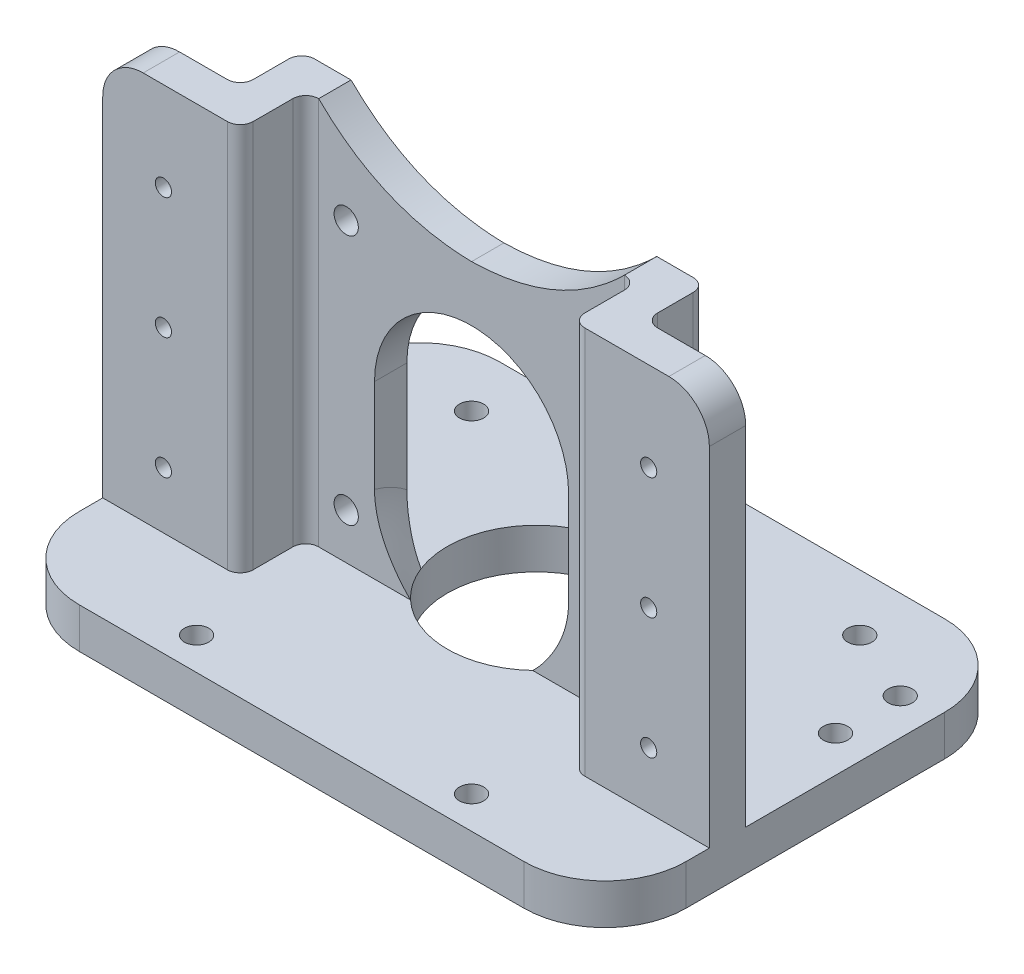
SolidWorks part; units mm, degrees
material "聚脂树脂"
ref_plane "前视基准面" through (0, 0, 0) normal (0, 0, 1) x (1, 0, 0)
ref_plane "上视基准面" through (0, 0, 0) normal (0, 1, 0) x (1, 0, 0)
ref_plane "右视基准面" through (0, 0, 0) normal (1, 0, 0) x (0, 0, -1)
other "Configuration Table"
sketch "草图1" plane through (0, 0, 0) normal (0, 1, 0) x (1, 0, 0)
  line L0 (0, 0) -> (58.6016, 0) construction
  line L1 (-37.5, -29) -> (37.5, -29)
  line L2 (-37.5, -29) -> (-37.5, 29)
  line L3 (-37.5, 29) -> (37.5, 29)
  line L4 (37.5, -29) -> (37.5, 29)
  line L5 (-37.5, -29) -> (37.5, 29) construction
  line L6 (-37.5, 29) -> (37.5, -29) construction
  line L7 (0, 0) -> (0, 47.0411) construction
  line L8 (0, 5) -> (44.8156, 5) construction
  circle A0 centre (0, 0) radius 11
  circle A1 centre (24, 16) radius 1.5
  circle A7 centre (-24, 16) radius 1.5
  circle A8 centre (17, -25) radius 1.5
  circle A9 centre (-17, -25) radius 1.5
  point P0 (0, 0)
  dimension "D3" = 22
  dimension "D4" = 3
  dimension "D7" = 11
  dimension "D8" = 3
  dimension "D10" = 34
  dimension "D1" = 58
  dimension "D2" = 75
  dimension "D5" = 24
  dimension "D6" = 5
  dimension "D9" = 30
extrude "凸台-拉伸1" add sketch "草图1" along normal blind 5
sketch "草图2" plane through (0, 5, 0) normal (0, 1, 0) x (1, 0, 0)
  line L0 (0, 0) -> (55.3583, 0) construction
  line L1 (0, 0) -> (0, 46.1954) construction
  line L2 (0, 0) -> (0, -38.3673) construction
  line L3 (-25, -4) -> (25, -4)
  line L4 (25, -4) -> (25, -11.6)
  line L5 (25, -11.6) -> (37.5, -11.6)
  line L6 (37.5, -11.6) -> (37.5, -16.1)
  line L7 (37.5, -16.1) -> (20.5, -16.1)
  line L8 (20.5, -16.1) -> (20.5, -8)
  line L9 (20.5, -8) -> (-20.5, -8)
  line L10 (-20.5, -16.1) -> (-20.5, -8)
  line L11 (-37.5, -16.1) -> (-20.5, -16.1)
  line L12 (-37.5, -11.6) -> (-37.5, -16.1)
  line L13 (-25, -11.6) -> (-37.5, -11.6)
  line L14 (-25, -4) -> (-25, -11.6)
  point P14 (0, -8)
  point P19 (0, -4)
  dimension "D1" = 25
  dimension "D2" = 7.6
  dimension "D3" = 20.5
  dimension "D4" = 8.1
  dimension "D5" = 17
  dimension "D6" = 4
  dimension "D7" = 4
extrude "凸台-拉伸2" add sketch "草图2" along normal blind 48
sketch "草图3" plane through (0, 0, 8) normal (0, 0, 1) x (1, 0, 0)
  line L0 (0, 0) -> (0, 69.1059) construction
  line L1 (0, 0) -> (57.4199, 0) construction
  line L2 (0, 5) -> (40.8093, 5) construction
  line L3 (-37.5, 5) -> (37.5, 5) construction
  line L4 (0, 26.15) -> (45.791, 26.15) construction
  line L5 (-30, 12) -> (-30, 61.5047) construction
  line L6 (-37.5, 5) -> (-20.5, 5) construction
  circle A0 centre (0, 26.15) radius 12
  circle A1 centre (15.5, 41.65) radius 1.5
  circle A2 centre (15.5, 10.65) radius 1.5
  circle A3 centre (-15.5, 10.65) radius 1.5
  circle A4 centre (-15.5, 41.65) radius 1.5
  circle A5 centre (-30, 12) radius 1
  circle A6 centre (-30, 27) radius 1
  circle A7 centre (-30, 42) radius 1
  circle A8 centre (30, 42) radius 1
  circle A9 centre (30, 27) radius 1
  circle A10 centre (30, 12) radius 1
  circle A11 centre (-30, 57) radius 1
  circle A12 centre (30, 57) radius 1
  dimension "D2" = 24
  dimension "D3" = 3
  dimension "D4" = 31
  dimension "D5" = 31
  dimension "D6" = 2
  dimension "D7" = 2
  dimension "D8" = 2
  dimension "D9" = 15
  dimension "D10" = 15
  dimension "D11" = 7
  dimension "D13" = 2
  dimension "D14" = 15
  dimension "D1" = 21.15
  dimension "D12" = 30
extrude "切除-拉伸1" cut sketch "草图3" along normal blind 60 and the other way blind 60
fillet "圆角3" radius 1.6 8 edges at (20.5, 29, 16.1) (20.5, 29, 8) (-20.5, 29, 16.1) (-20.5, 29, 8) (25, 29, 11.6) (25, 29, 4) (-25, 29, 4) (-25, 29, 11.6)
sketch "草图4" plane through (0, 5, 0) normal (0, 1, 0) x (1, 0, 0)
  line L0 (0, 0) -> (50.2662, 0) construction
  line L1 (0, 0) -> (0, 50.3436) construction
  line L2 (33, -23.9509) -> (33, 23.9509) construction
  circle A0 centre (33, 12) radius 1.5
  circle A1 centre (33, 4) radius 1.5
  circle A2 centre (-33, 4) radius 1.5
  circle A3 centre (-33, 12) radius 1.5
  point P11 (33, 0)
  point P17 (-33, 0)
  dimension "D1" = 3
  dimension "D2" = 3
  dimension "D3" = 8
  dimension "D4" = 12
  dimension "D5" = 33
extrude "切除-拉伸2" cut sketch "草图4" against normal blind 10
sketch "草图5" plane through (0, 5, 0) normal (0, 1, 0) x (1, 0, 0)
  line L0 (-37.5, 23) -> (-37.5, 29)
  line L1 (-37.5, 29) -> (-37.5, -11.6) construction
  line L2 (-37.5, 29) -> (37.5, 29)
  line L3 (37.5, 29) -> (37.5, 23)
  line L4 (37.5, -11.6) -> (37.5, 29) construction
  line L5 (37.5, 23) -> (-37.5, 23)
  dimension "D1" = 6
extrude "切除-拉伸3" cut sketch "草图5" against normal blind 10
fillet "圆角4" radius 10 4 edges at (37.5, 2.5, -23) (-37.5, 2.5, -23) (37.5, 2.5, 29) (-37.5, 2.5, 29)
sketch "草图6" plane through (0, 0, 8) normal (0, 0, 1) x (1, 0, 0)
  line L0 (0, 0) -> (0, 81.7287) construction
  line L1 (18.9, 53) -> (-18.9, 53)
  spline S0 degree 2 poles (-18.9, 53) (-11.0346, 45.2022) (0, 45) knots 0 0 0 1 1 1
  spline S1 degree 2 poles (18.9, 53) (11.0346, 45.2022) (0, 45) knots 0 0 0 1 1 1
  dimension "D1" = 8
  dimension "D2" = 6
  dimension "D3" = 10
extrude "切除-拉伸4" cut sketch "草图6" against normal blind 10
fillet "圆角5" radius 5 2 edges at (37.5, 53, 13.85) (-37.5, 53, 13.85)
sketch "草图7" plane through (0, 0, 8) normal (0, 0, 1) x (1, 0, 0)
  line L0 (0, 0) -> (0, 56.32) construction
  line L1 (-27.5, 0) -> (27.5, 0) construction
  line L2 (0, 5) -> (12, 5)
  line L3 (-18.9, 5) -> (-7.5498, 5) construction
  line L4 (12, 5) -> (12, 26.15)
  line L5 (12, 26.15) -> (-12, 26.15)
  line L6 (-12, 5) -> (-12, 26.15)
  line L7 (0, 5) -> (-12, 5)
  circle A0 centre (0, 26.15) radius 12 construction
  point P11 (0, 26.15)
  dimension "D1" = 12
extrude "切除-拉伸5" cut sketch "草图7" against normal blind 10
fillet "圆角6" radius 10 2 edges at (12, 5, 6) (-12, 5, 6)
